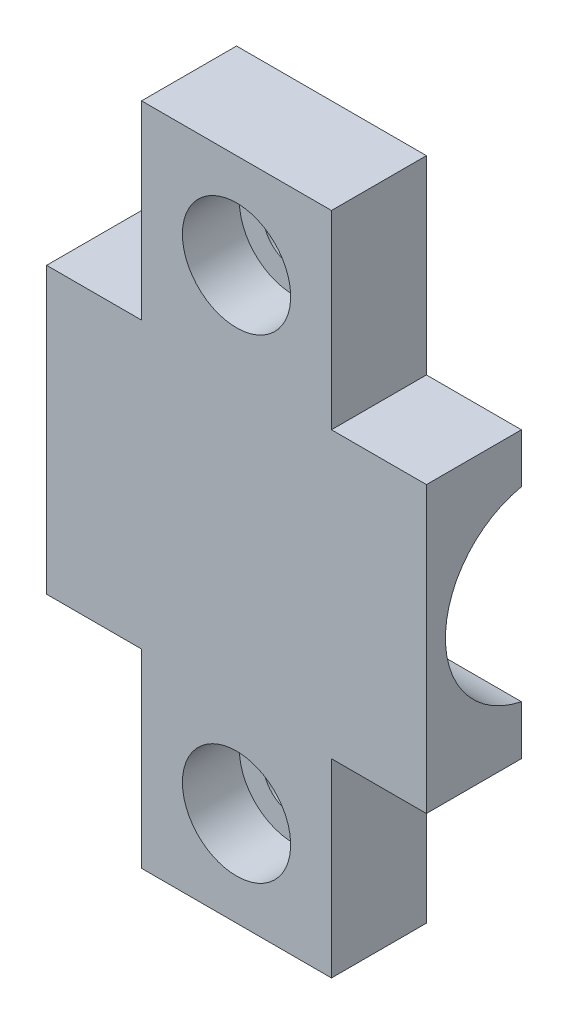
SolidWorks part; units mm, degrees
ref_plane "Front Plane" through (0, 0, 0) normal (1, 0, 0) x (0, 1, 0)
ref_plane "Top Plane" through (0, 0, 0) normal (0, 0, 1) x (0, 1, 0)
ref_plane "Right Plane" through (0, 0, 0) normal (0, 1, 0) x (-1, 0, 0)
sketch "Sketch1" plane through (0, 0, 0) normal (1, 0, 0) x (0, 1, 0)
  line L0 (0, 5) -> (0, 1) construction
  line L1 (17.5, 1) -> (4.899, 1)
  line L2 (-17.5, 1) -> (-17.5, 6)
  line L3 (17.5, 1) -> (17.5, 6)
  line L4 (17.5, 6) -> (-17.5, 6)
  line L5 (0, 1) -> (-4.899, 1) construction
  line L6 (-4.899, 1) -> (-17.5, 1)
  line L7 (4.899, 1) -> (0, 1) construction
  arc A0 (4.899, 1) -> (-4.899, 1) centre (0, 0) ccw
  arc A1 (-4.899, 1) -> (4.899, 1) centre (0, 0) ccw construction
  point P8 (0, 1)
  dimension "D1" = 10
  dimension "D2" = 4
  dimension "D3" = 35
  dimension "D4" = 5
extrude "Boss-Extrude1" add sketch "Sketch1" along normal blind 20 contours A0 L1 L3 L4 L2 L6 region at (0, 11.1995, 1.3536)
sketch "Sketch2" plane through (0, 0, 6) normal (0, 0, 1) x (1, 0, 0)
  line L0 (0, 0) -> (20, 0) construction
  line L1 (20, 17.5) -> (20, -17.5) construction
  line L2 (10, 12.5) -> (10, -12.5) construction
  line L3 (5, -7.5) -> (5, 7.5) construction
  line L4 (0, 17.5) -> (5, 17.5)
  line L5 (0, 17.5) -> (0, 7.5)
  line L6 (0, 7.5) -> (5, 7.5)
  line L7 (5, 17.5) -> (5, 7.5)
  line L8 (20, 17.5) -> (15, 17.5)
  line L9 (20, 17.5) -> (20, 7.5)
  line L10 (20, 7.5) -> (15, 7.5)
  line L11 (15, 17.5) -> (15, 7.5)
  line L12 (20, -17.5) -> (15, -17.5)
  line L13 (20, -17.5) -> (20, -7.5)
  line L14 (20, -7.5) -> (15, -7.5)
  line L15 (15, -17.5) -> (15, -7.5)
  line L16 (0, -17.5) -> (5, -17.5)
  line L17 (0, -17.5) -> (0, -7.5)
  line L18 (0, -7.5) -> (5, -7.5)
  line L19 (5, -17.5) -> (5, -7.5)
  line L20 (5, 7.5) -> (15, 7.5) construction
  circle A0 centre (10, -12.5) radius 1.6
  circle A1 centre (10, -12.5) radius 2.85
  circle A2 centre (10, 12.5) radius 1.6
  circle A3 centre (10, 12.5) radius 2.85
  point P8 (10, 0)
  point P32 (10, 7.5)
  point P33 (5, 0)
  point P34 (0, 0)
  line M2 (0, 17.5) -> (0, -17.5)
  line M3 (0, -17.5) -> (20, -17.5)
  line M4 (20, -17.5) -> (20, 17.5)
  line M5 (20, 17.5) -> (0, 17.5)
  dimension "D2" = 3.2
  dimension "D3" = 3.2
  dimension "D4" = 5.7
  dimension "D5" = 5.7
  dimension "D1" = 25
  dimension "D6" = 15
  dimension "D7" = 10
extrude "Cut-Extrude1" cut sketch "Sketch2" against normal through all both and the other way through all contours L19 L18 M3 M2 | L7 L6 M5 M2 | L11 L10 M5 M4 | L15 L14 M3 M4 | A0 | A2 region at (2.5, 12.5, 6) region at (17.5, 12.5, 6) region at (2.5, -12.5, 6) region at (17.5, -12.5, 6) region at (10, -12.5, 6) region at (10, 12.5, 6)
extrude "Cut-Extrude2" cut sketch "Sketch2<3>" against normal blind 3 and the other way through all contours A1 A0 | A3 A2 region at (7.2306, -12.5, 6) region at (7.2306, 12.5, 6)
sketch "Sketch2<3>" plane through (0, 0, 6) normal (0, 0, 1) x (1, 0, 0) same geometry as "Sketch2"
